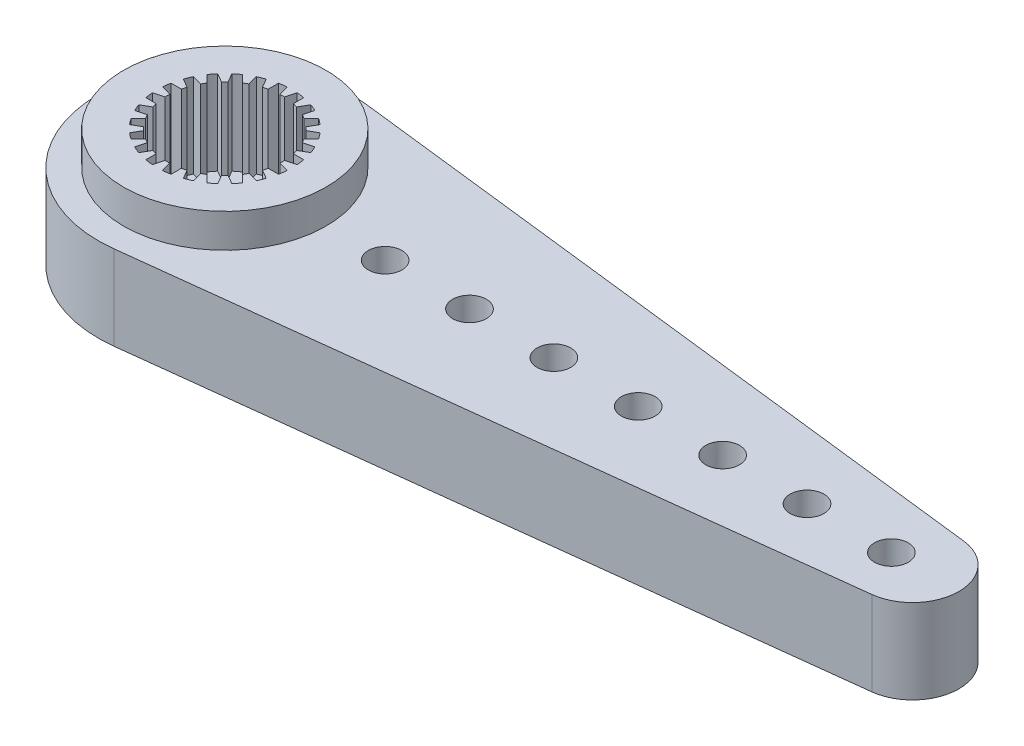
SolidWorks part; units mm, degrees
ref_plane "Plan de face" through (0, 0, 0) normal (0, 0, 1) x (1, 0, 0)
ref_plane "Plan de dessus" through (0, 0, 0) normal (0, 1, 0) x (1, 0, 0)
ref_plane "Plan de droite" through (0, 0, 0) normal (1, 0, 0) x (0, 0, -1)
sketch "Esquisse1" plane through (0, 0, 0) normal (0, 1, 0) x (1, 0, 0)
  line L0 (0.8742, -7.4489) -> (41.0706, -2.7313)
  line L1 (41.0706, 2.7313) -> (0.8742, 7.4489)
  line L2 (-7.5, 27.3999) -> (-7.5, -15.4168) construction
  line L3 (-7.5, -15.4168) -> (43.5, -15.4168) construction
  line L4 (43.5, -15.4168) -> (43.5, 24.8813) construction
  arc A0 (0.8742, 7.4489) -> (0.8742, -7.4489) centre (0, 0) ccw
  arc A1 (41.0706, -2.7313) -> (41.0706, 2.7313) centre (40.75, 0) ccw
  circle A2 centre (0, 0) radius 1.6
  dimension "D1" = 2.75
  dimension "D2" = 7.5
  dimension "D4" = 3.2
  dimension "D3" = 51
extrude "Boss.-Extru.1" add sketch "Esquisse1" along normal blind 8
sketch "Esquisse2" plane through (0, 8, 0) normal (0, 1, 0) x (1, 0, 0)
  line L0 (0, 0) -> (46.1588, 0) construction
  line L1 (-7.5, 15.192) -> (-7.5, -12.3349) construction
  circle A0 centre (9.5, 0) radius 1
  arc A1 (0.8742, 7.4489) -> (0.8742, -7.4489) centre (0, 0) ccw construction
  dimension "D1" = 2
  dimension "D2" = 17
extrude "Enlèv. mat.-Extru.1" cut sketch "Esquisse2" against normal blind 8
pattern_linear "Répétition linéaire1" count 7 spacing 5 along (1, 0, 0) of "Enlèv. mat.-Extru.1"
sketch "Esquisse3" plane through (0, 8, 0) normal (0, 1, 0) x (1, 0, 0)
  line L1 (-12.783, 10.2172) -> (50.2427, 10.2172)
  line L2 (-12.783, 10.2172) -> (-12.783, -12.2303)
  line L3 (-12.783, -12.2303) -> (50.2427, -12.2303)
  line L4 (50.2427, 10.2172) -> (50.2427, -12.2303)
  circle A0 centre (0, 0) radius 6
  dimension "D1" = 12
extrude "Enlèv. mat.-Extru.2" cut sketch "Esquisse3" against normal blind 2
sketch "Esquisse4" plane through (0, 0, 0) normal (0, -1, 0) x (1, 0, 0)
  line L1 (-13.4769, 12.3588) -> (51.6733, 12.3588)
  line L2 (-13.4769, 12.3588) -> (-13.4769, -11.2271)
  line L3 (-13.4769, -11.2271) -> (51.6733, -11.2271)
  line L4 (51.6733, 12.3588) -> (51.6733, -11.2271)
  circle A0 centre (0, 0) radius 4.65
  dimension "D1" = 9.3
extrude "Enlèv. mat.-Extru.3" cut sketch "Esquisse4" against normal blind 1
sketch "Esquisse5" plane through (0, 0, 0) normal (0, -1, 0) x (1, 0, 0)
  circle A0 centre (0, 0) radius 2.75
  dimension "D1" = 5.5
extrude "Enlèv. mat.-Extru.4" cut sketch "Esquisse5" against normal blind 1
chamfer "Chanfrein1" distance 1 angle 45 1 edges at (0, 1, -4.65)
sketch "Esquisse6" plane through (0, 8, 0) normal (0, 1, 0) x (1, 0, 0)
  circle A0 centre (0, 0) radius 4
  dimension "D1" = 8
extrude "Enlèv. mat.-Extru.5" cut sketch "Esquisse6" against normal blind 5
sketch "Esquisse7" plane through (0, 8, 0) normal (0, 1, 0) x (1, 0, 0)
  line L0 (0, 0) -> (0, -6.8034) construction
  line L1 (0, -6.8034) -> (2.7804, -4) construction
  line L2 (2.7804, -4) -> (-2.8896, -4) construction
  line L3 (0.3, -4) -> (0.1392, -3.4)
  line L4 (0.1392, -3.4) -> (-0.1392, -3.4)
  line L5 (-0.1392, -3.4) -> (-0.3, -4)
  line L6 (-0.3, -4) -> (0.3, -4)
  circle A0 centre (0, 0) radius 4 construction
  dimension "D1" = 0.6
  dimension "D2" = 0.6
  dimension "D3" = 15
extrude "Boss.-Extru.2" add sketch "Esquisse7" against normal up to surface (5 mm away) up to face at (0, 3, 1.6)
pattern_circular "Répétition circulaire1" count 24 over 360 about axis through (0, 8, 0) along (0, -1, 0) of "Boss.-Extru.2"
scale "Escala2" scale about centroid uniform scaling yes scale factor 0.7
scale "Escala5" scale about centroid uniform scaling yes scale factor 0.8
scale "Escala6" scale about centroid uniform scaling yes scale factor 0.9
scale "Escala7" scale about centroid uniform scaling yes scale factor 0.9
scale "Escala8" scale about centroid uniform scaling yes scale factor 1.05
scale "Escala9" scale about centroid uniform scaling yes scale factor 1.2
